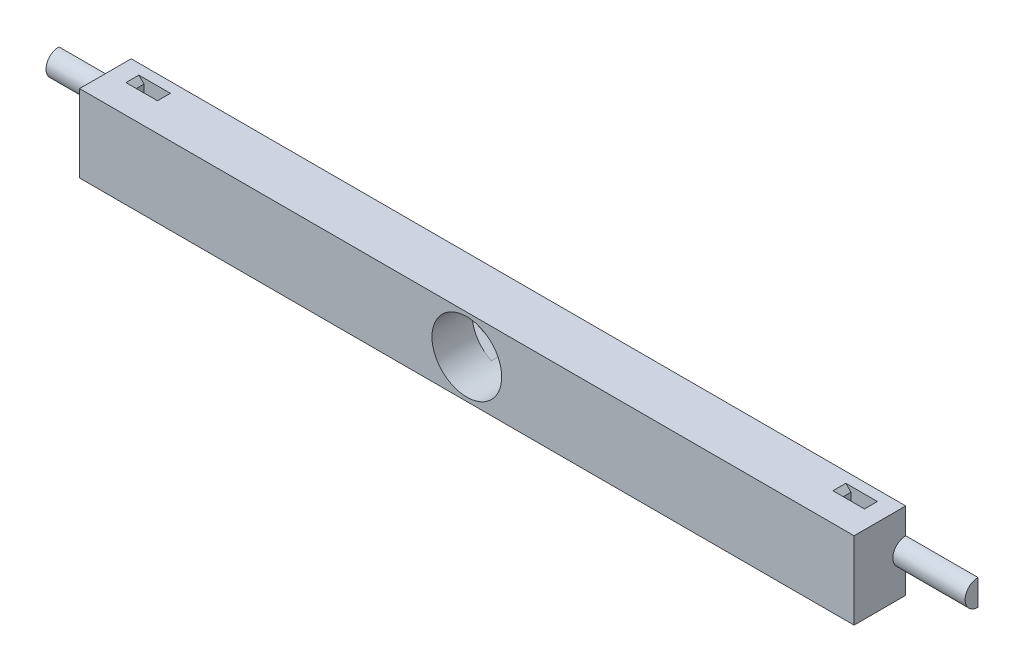
SolidWorks part; units mm, degrees
ref_plane "前视基准面" through (0, 0, 0) normal (0, 0, 1) x (1, 0, 0)
ref_plane "上视基准面" through (0, 0, 0) normal (0, 1, 0) x (1, 0, 0)
ref_plane "右视基准面" through (0, 0, 0) normal (1, 0, 0) x (0, 0, -1)
other "Configuration Table"
sketch "草图1" plane through (0, 0, 0) normal (0, 0, 1) x (1, 0, 0)
  line L0 (0, 0) -> (79.8665, 0) construction
  line L1 (0, 0) -> (0, 25.0088) construction
  line L2 (-150, 0) -> (-150, 30)
  line L3 (-150, 30) -> (150, 30)
  line L4 (150, 30) -> (150, 0)
  line L5 (150, 0) -> (-150, 0)
  point P7 (0, 30)
  dimension "D1" = 300
  dimension "D2" = 30
extrude "凸台-拉伸1" add sketch "草图1" along normal blind 20 contours L2 L3 L4 L5
sketch "草图2" plane through (-150, 0, 0) normal (-1, 0, 0) x (0, 0, 1)
  line L0 (0, 0) -> (0, 30) construction
  line L1 (0, 0) -> (0, 30) construction
  line L3 (0, 15) -> (20, 15) construction
  line L6 (0, 20) -> (0, 10)
  arc A0 (0, 10) -> (0, 20) centre (0, 15) ccw
  dimension "D1" = 5
extrude "凸台-拉伸2" add sketch "草图2" along normal blind 28 and the other way blind 328 contours L6 A0
sketch "草图3" plane through (0, 0, 0) normal (0, 0, -1) x (-1, 0, 0)
  line L0 (0, 0) -> (0, 129.1579) construction
  line L1 (-178, 15) -> (178, 15) construction
  line L2 (-6.0203, 27.0833) -> (-20.8412, 19.6991)
  line L3 (6.0203, 27.0833) -> (20.8412, 19.6991)
  line L4 (6.0203, 2.9167) -> (20.8412, 10.3009)
  line L5 (-6.0203, 2.9167) -> (-20.8412, 10.3009)
  circle A0 centre (0, 15) radius 4
  circle A1 centre (0, 15) radius 6
  circle A2 centre (0, 15) radius 13.25
  circle A3 centre (18.5, 15) radius 2.4
  circle A4 centre (0, 15) radius 13.5
  circle A5 centre (-18.5, 15) radius 2.4
  arc A6 (-20.8412, 19.6991) -> (-20.8412, 10.3009) centre (-18.5, 15) ccw
  arc A7 (20.8412, 19.6991) -> (20.8412, 10.3009) centre (18.5, 15) cw
  point P20 (-23.75, 15)
  dimension "D1" = 8
  dimension "D2" = 2
  dimension "D4" = 4.8
  dimension "D6" = 0.25
  dimension "D7" = 10.5
  dimension "D5" = 18.5
  dimension "D3" = 7.25
extrude "切除-拉伸1" cut sketch "草图3" against normal through all contours A0 region at (0, 15, 0)
extrude "切除-拉伸2" cut sketch "草图3<3>" against normal through all contours A1 A0 region at (5.8303, 15, 0)
sketch "草图3<3>" plane through (0, 0, 0) normal (0, 0, -1) x (-1, 0, 0) same geometry as "草图3"
extrude "切除-拉伸3" cut sketch "草图3<4>" against normal through all contours A2 A1 | A4 A2 region at (0, 28.4618, 0) region at (12.8752, 15, 0)
sketch "草图3<4>" plane through (0, 0, 0) normal (0, 0, -1) x (-1, 0, 0) same geometry as "草图3"
extrude "切除-拉伸4" cut sketch "草图3<5>" against normal blind 4.5 contours L2 A6 L5 A4 A5 | A7 L3 A4 L4 A3 region at (13.7997, 15, 0) region at (-13.2971, 23.1229, 0)
sketch "草图3<5>" plane through (0, 0, 0) normal (0, 0, -1) x (-1, 0, 0) same geometry as "草图3"
extrude "切除-拉伸5" cut sketch "草图3<6>" against normal blind 5 contours A5 | A3 region at (-18.5, 15, 0) region at (18.5, 15, 0)
sketch "草图3<6>" plane through (0, 0, 0) normal (0, 0, -1) x (-1, 0, 0) same geometry as "草图3"
sketch "草图4" plane through (0, 30, 0) normal (0, 1, 0) x (1, 0, 0)
  line L0 (0, 0) -> (0, 98.3857) construction
  line L1 (0, 0) -> (-201.6217, 0) construction
  line L2 (-150, -20) -> (-150, 0) construction
  line L3 (-143.03, -9) -> (-130.81, -9)
  line L4 (-143.03, -9) -> (-143.03, -4)
  line L5 (-143.03, -4) -> (-130.81, -4)
  line L6 (-130.81, -9) -> (-130.81, -4)
  line L7 (-143.03, -9) -> (-130.81, -4) construction
  line L8 (-143.03, -4) -> (-130.81, -9) construction
  point P3 (-136.92, -6.5)
  point P4 (0, 0)
  dimension "D1" = 5
  dimension "D2" = 12.22
  dimension "D3" = 4
  dimension "D4" = 13.08
ref_plane "基准面1" through (0, 28, 0) normal (0, 1, 0) x (1, 0, 0)
sketch "草图5" plane through (0, 28, 0) normal (0, 1, 0) x (1, 0, 0)
  line L0 (-143.03, -9) -> (-143.03, -4) construction
  line L1 (-141.03, -9) -> (-132.81, -9)
  line L2 (-141.03, -9) -> (-141.03, -4)
  line L3 (-141.03, -4) -> (-132.81, -4)
  line L4 (-132.81, -9) -> (-132.81, -4)
  line L5 (-141.03, -9) -> (-132.81, -4) construction
  line L6 (-141.03, -4) -> (-132.81, -9) construction
  line L8 (-143.03, -9) -> (-130.81, -9) construction
  line L9 (-130.81, -9) -> (-130.81, -4) construction
  point P0 (-136.92, -6.5)
  dimension "D1" = 2
  dimension "D2" = 5
  dimension "D3" = 0
  dimension "D4" = 2
sketch "草图6" plane through (0, 0, 0) normal (0, -1, 0) x (1, 0, 0)
  line L1 (-143.03, 4) -> (-130.81, 4)
  line L2 (-143.03, 4) -> (-143.03, 9)
  line L3 (-143.03, 9) -> (-130.81, 9)
  line L4 (-130.81, 4) -> (-130.81, 9)
  line L5 (-143.03, 4) -> (-130.81, 9) construction
  line L6 (-143.03, 9) -> (-130.81, 4) construction
  point P0 (-136.92, 6.5)
ref_plane "基准面2" through (0, 2, 0) normal (0, -1, 0) x (-1, 0, 0)
sketch "草图7" plane through (0, 2, 0) normal (0, -1, 0) x (-1, 0, 0)
  line L1 (132.81, -9) -> (141.03, -9)
  line L2 (132.81, -9) -> (132.81, -4)
  line L3 (132.81, -4) -> (141.03, -4)
  line L4 (141.03, -9) -> (141.03, -4)
  line L5 (132.81, -9) -> (141.03, -4) construction
  line L6 (132.81, -4) -> (141.03, -9) construction
  point P0 (136.92, -6.5)
loft "切除-放样2" cut profiles "草图6", "草图7"
loft "切除-放样3" cut profiles "草图4", "草图5"
sketch "草图9" plane through (0, 28, 0) normal (0, 1, 0) x (1, 0, 0)
  line L1 (-141.03, -9) -> (-132.81, -9)
  line L2 (-141.03, -9) -> (-141.03, -4)
  line L3 (-141.03, -4) -> (-132.81, -4)
  line L4 (-132.81, -9) -> (-132.81, -4)
  line L5 (-141.03, -9) -> (-132.81, -4) construction
  line L6 (-141.03, -4) -> (-132.81, -9) construction
  point P0 (-136.92, -6.5)
extrude "切除-拉伸6" cut sketch "草图9" against normal through all
mirror "镜向2" about plane through (0, 0, 0) normal (1, 0, 0) of "切除-拉伸6", "切除-放样3", "切除-放样2"
sketch "草图11" plane through (0, 0, 0) normal (0, 0, -1) x (-1, 0, 0)
  line L0 (150, 30) -> (-150, 30) construction
  line L2 (-150, 30) -> (-150, 20) construction
  circle A0 centre (-136.92, 15) radius 2.55
  dimension "D1" = 5.1
  dimension "D2" = 15
  dimension "D3" = 13.08
extrude "切除-拉伸7" cut sketch "草图11" against normal up to next contours A0
mirror "镜向3" about plane through (0, 0, 0) normal (1, 0, 0) of "切除-拉伸7"
